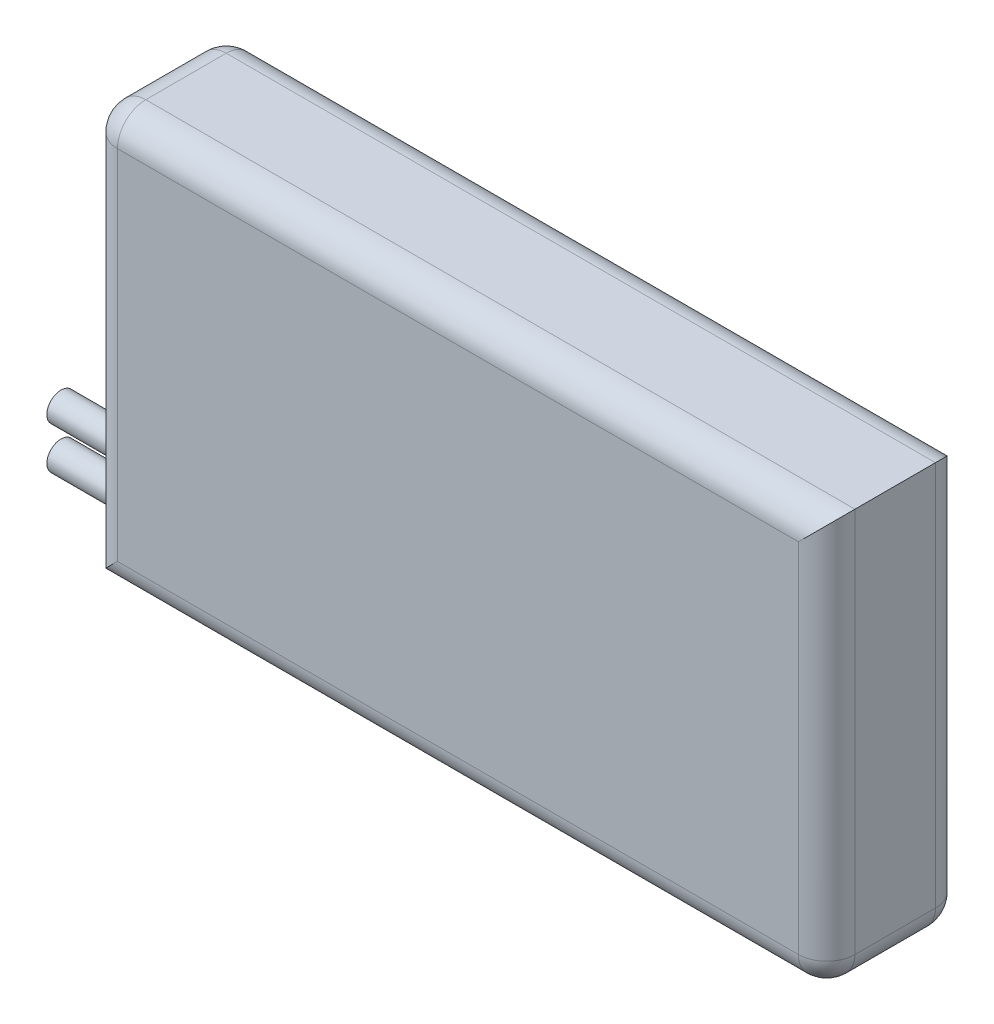
SolidWorks part; units mm, degrees
ref_plane "Front Plane" through (0, 0, 0) normal (0, 0, 1) x (1, 0, 0)
ref_plane "Top Plane" through (0, 0, 0) normal (0, 1, 0) x (1, 0, 0)
ref_plane "Right Plane" through (0, 0, 0) normal (1, 0, 0) x (0, 0, -1)
sketch "Sketch1" plane through (0, 0, 0) normal (0, 0, 1) x (1, 0, 0)
  line L1 (26.1, -14.65) -> (-26.1, -14.65)
  line L2 (26.1, -14.65) -> (26.1, 14.65)
  line L3 (26.1, 14.65) -> (-26.1, 14.65)
  line L4 (-26.1, -14.65) -> (-26.1, 14.65)
  line L5 (26.1, -14.65) -> (-26.1, 14.65) construction
  line L6 (26.1, 14.65) -> (-26.1, -14.65) construction
  point P0 (0, 0)
  dimension "D1" = 52.2
  dimension "D2" = 29.3
extrude "Boss-Extrude1" add sketch "Sketch1" along normal blind 9.7
sketch "Sketch2" plane through (-26.1, 0, 0) normal (-1, 0, 0) x (0, 0, 1)
  line L0 (9.7, 14.65) -> (9.7, -14.65) construction
  line L1 (9.7, -14.65) -> (0, -14.65) construction
  circle A0 centre (4.7, -13.15) radius 1
  circle A1 centre (4.7, -10.15) radius 1
  dimension "D1" = 2
  dimension "D2" = 2
  dimension "D3" = 5
  dimension "D4" = 5
  dimension "D6" = 1.5
  dimension "D5" = 3
extrude "Boss-Extrude2" add sketch "Sketch2" along normal blind 7
fillet "Fillet1" radius 2 4 edges at (26.1, 0, 9.7) (0, 14.65, 9.7) (-26.1, 0, 9.7) (0, -14.65, 9.7)
fillet "Fillet2" radius 2 4 edges at (0, 14.65, 0) (26.1, 0, 0) (0, -14.65, 0) (-26.1, 0, 0)
fillet "Fillet3" radius 2 3 edges at (-26.1, 14.65, 4.85) (-25.5142, 14.0642, 9.1142) (-25.5142, 14.0642, 0.5858)
fillet "Fillet4" radius 2 3 edges at (26.1, -14.65, 4.85) (25.5142, -14.0642, 9.1142) (25.5142, -14.0642, 0.5858)
